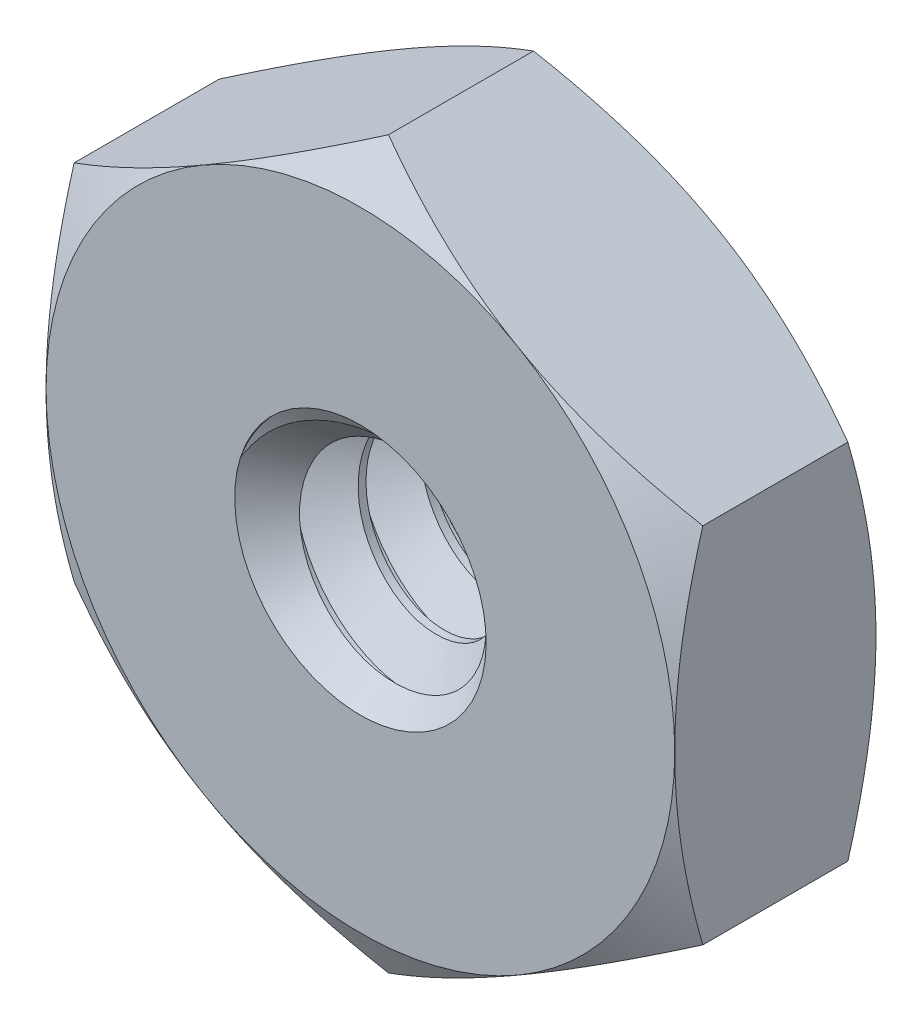
SolidWorks part; units mm, degrees
ref_plane "Front" through (0, 0, 0) normal (0, 0, 1) x (1, 0, 0)
ref_plane "Top" through (0, 0, 0) normal (0, 1, 0) x (1, 0, 0)
ref_plane "Right" through (0, 0, 0) normal (1, 0, 0) x (0, 0, -1)
sketch "Sketch1" plane through (0, 0, 0) normal (0, 0, 1) x (1, 0, 0)
  line L1 (-1.25, 0.7217) -> (-1.25, -0.7217)
  line L2 (-1.25, -0.7217) -> (0, -1.4434)
  line L3 (0, -1.4434) -> (1.25, -0.7217)
  line L4 (1.25, -0.7217) -> (1.25, 0.7217)
  line L5 (1.25, 0.7217) -> (0, 1.4434)
  line L6 (0, 1.4434) -> (-1.25, 0.7217)
  circle A0 centre (0, 0) radius 1.25 construction
  circle A1 centre (0, 0) radius 0.5 construction
  point P10 (0, 0.5)
  dimension "hex" = 2.5
  dimension "dia" = 1
extrude "Extrude1" add sketch "Sketch1" along normal mid plane 0.8
sketch "Sketch4" plane through (0, 0, -0.4) normal (0, 0, -1) x (-1, 0, 0)
  circle A0 centre (0, 0) radius 0.5 construction
  circle A1 centre (0, 0) radius 0.5
sketch "Sketch10" plane through (0, 0, 0.4) normal (0, 0, 1) x (1, 0, 0)
  circle A0 centre (0, 0) radius 0.5 construction
  circle A1 centre (0, 0) radius 0.5
extrude "Cut-Extrude2" cut sketch "Sketch10" against normal through all draft 45
sketch "Sketch11" plane through (0, 0, -0.4) normal (0, 0, -1) x (-1, 0, 0)
  circle A0 centre (0, 0) radius 0.5 construction
  circle A1 centre (0, 0) radius 0.5
extrude "Cut-Extrude3" cut sketch "Sketch11" against normal through all draft 45
sketch "Sketch13" plane through (0, 0, -0.4) normal (0, 0, -1) x (-1, 0, 0)
  circle A0 centre (0, 0) radius 0.5 construction
  circle A1 centre (0, 0) radius 0.5
extrude "Boss-Extrude1" add sketch "Sketch13" against normal up to vertex (0.8 mm away) separate body up to point (-1.25, 0.7217, 0.4)
curve "Helix/Spiral3" pitch 0.25 height 0.8 turns 3.2
sketch "Sketch12" plane through (0, 0, 0) normal (1, 0, 0) x (0, 0, -1)
  line L0 (0.6187, 0.5) -> (0.4, 0.5)
  line L1 (0.6187, 0.5) -> (0.525, 0.3376)
  line L2 (0.525, 0.3376) -> (0.4937, 0.3376)
  line L3 (0.4937, 0.3376) -> (0.4, 0.5)
  line L4 (0.5094, 0.3376) -> (0.5094, 0.5) construction
  line L5 (0.4469, 0.4188) -> (0.5719, 0.4188) construction
  dimension "D1" = 60
  dimension "D2" = 0.0312
  dimension "D3" = 0.125
sweep "Cut-Sweep1" cut profiles "Sketch12" path "Helix/Spiral3"
combine bodies "Combine1" operation type subtract main body 116 bodies to subtract 118
sketch "Sketch7" plane through (0, 0, 0.4) normal (0, 0, 1) x (1, 0, 0)
  circle A0 centre (0, 0) radius 1.25 construction
  circle A1 centre (0, 0) radius 1.25
extrude "Extrude2" cut sketch "Sketch7" against normal blind 25.4 draft 60 flip side to cut
mirror "Mirror2" about plane through (0, 0, 0) normal (0, 0, 1) of "Extrude2"
sketch "Sketch8" plane through (0, 0, 0.4) normal (0, 0, 1) x (1, 0, 0)
  line L0 (-0.3536, 0.3536) -> (0, 0) construction
  line L1 (0, -0.6275) -> (0, 0.6275) construction
  circle A1 centre (0, 0) radius 0.5 construction
  point P0 (-0.3536, 0.3536)
  dimension "D1" = 45
sketch "Sketch14" plane through (0, 0, 0.4) normal (0, 0, 1) x (1, 0, 0)
  line L0 (0, 0) -> (-0.5, 0) construction
  arc A0 (0, 0.5) -> (-0.477, 0.15) centre (0, 0) ccw construction
equation "\"D3@Helix/Spiral3\" = \"length@Extrude1\" "
equation "\"D2@Sketch12\" = \"D4@Helix/Spiral3\"*.125"
equation "\"D3@Sketch12\" = \"D4@Helix/Spiral3\"*.50"
